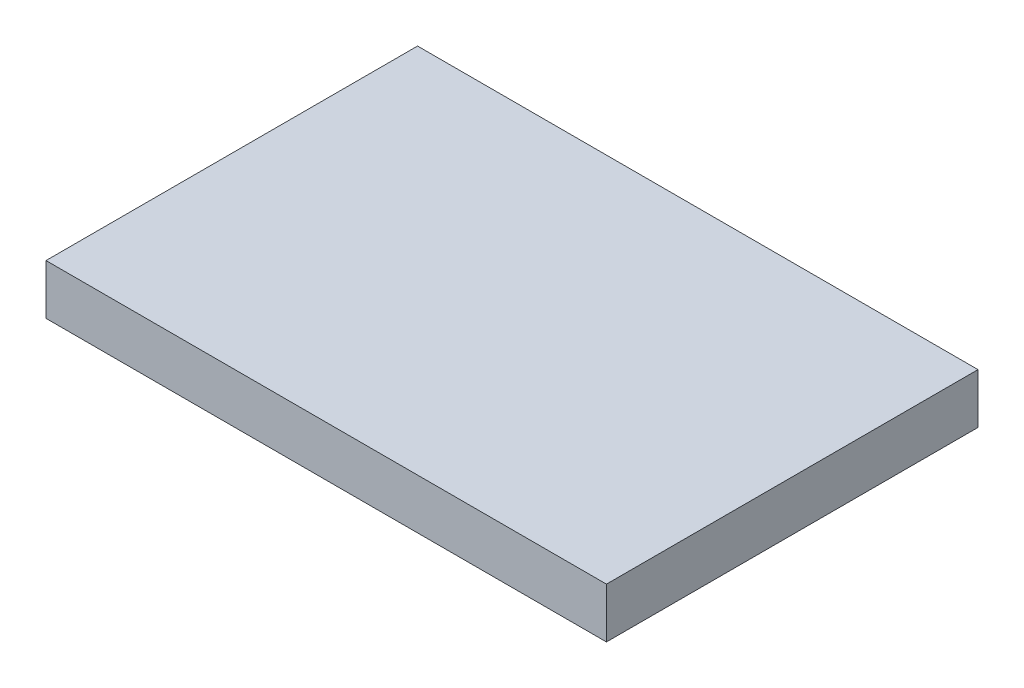
SolidWorks part; units mm, degrees
ref_plane "Front" through (0, 0, 0) normal (0, 0, 1) x (1, 0, 0)
ref_plane "Top" through (0, 0, 0) normal (0, 1, 0) x (1, 0, 0)
ref_plane "Right" through (0, 0, 0) normal (1, 0, 0) x (0, 0, -1)
sketch "Sketch1" plane through (0, 0, 0) normal (0, 1, 0) x (1, 0, 0)
  line L1 (-1447.8, 825.5) -> (1447.8, 825.5)
  line L2 (-1447.8, 825.5) -> (-1447.8, -825.5)
  line L3 (-1447.8, -825.5) -> (1447.8, -825.5)
  line L4 (1447.8, 825.5) -> (1447.8, -825.5)
  line L5 (-1447.8, 825.5) -> (1447.8, -825.5) construction
  line L6 (-1447.8, -825.5) -> (1447.8, 825.5) construction
  point P0 (0, 0)
  dimension "D1" = 2895.6
  dimension "D2" = 1651
extrude "Boss-Extrude1" [suppressed] add sketch "Sketch1" along normal blind 1473.2
sketch "Sketch2" [suppressed] plane through (0, 0, 0) normal (0, -1, 0) x (1, 0, 0)
  line L0 (0, 0) -> (2162.175, 0) construction
  line L1 (1447.8, 825.5) -> (1447.8, -825.5) construction
  line L2 (1752.6, 663.575) -> (2571.75, 663.575)
  line L3 (1752.6, 663.575) -> (1752.6, -663.575)
  line L4 (1752.6, -663.575) -> (2571.75, -663.575)
  line L5 (2571.75, 663.575) -> (2571.75, -663.575)
  line L6 (1752.6, 663.575) -> (2571.75, -663.575) construction
  line L7 (1752.6, -663.575) -> (2571.75, 663.575) construction
  dimension "D1" = 1327.15
  dimension "D2" = 819.15
  dimension "D3" = 304.8
extrude "Boss-Extrude2" [suppressed] add sketch "Sketch2" against normal blind 736.6 separate body
sketch "Sketch3" plane through (0, 0, 0) normal (0, 1, 0) x (-1, 0, 0)
  line L2 (1704.975, 1130.3) -> (-1704.975, 1130.3)
  line L3 (1704.975, 1130.3) -> (1704.975, -1130.3)
  line L4 (1704.975, -1130.3) -> (-1704.975, -1130.3)
  line L5 (-1704.975, 1130.3) -> (-1704.975, -1130.3)
  line L6 (1704.975, 1130.3) -> (-1704.975, -1130.3) construction
  line L7 (1704.975, -1130.3) -> (-1704.975, 1130.3) construction
  dimension "D1" = 2260.6
  dimension "D2" = 3409.95
  dimension "D4" = 2260.6
  dimension "D5" = 3409.95
extrude "Boss-Extrude3" add sketch "Sketch3" along normal blind 304.8 separate body
